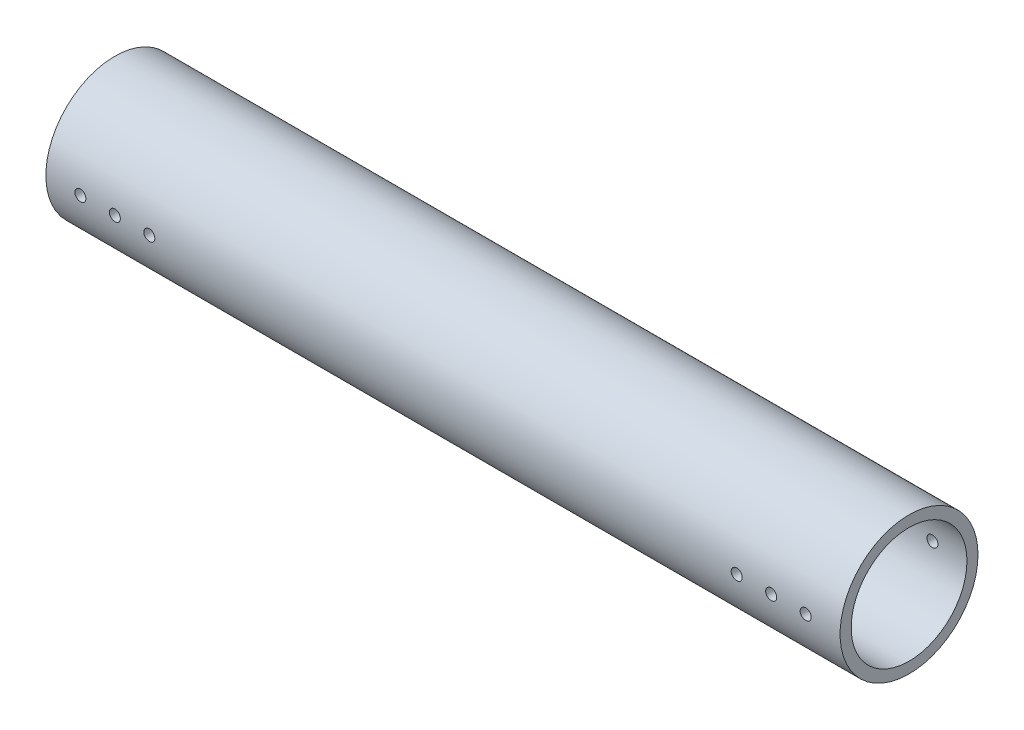
SolidWorks part; units mm, degrees
material "Zoltek Panex 33"
ref_plane "Спереди" through (0, 0, 0) normal (0, 0, 1) x (1, 0, 0)
ref_plane "Сверху" through (0, 0, 0) normal (0, 1, 0) x (1, 0, 0)
ref_plane "Справа" through (0, 0, 0) normal (1, 0, 0) x (0, 0, -1)
other "Configuration Table"
sketch "Эскиз2" plane through (0, 0, 0) normal (1, 0, 0) x (0, 0, -1)
  circle A0 centre (0, 0) radius 25
  circle A1 centre (0, 0) radius 21
  dimension "D1" = 50
  dimension "D2" = 42
extrude "Бобышка-Вытянуть2" add sketch "Эскиз2" along normal blind 288
ref_plane "Плоскость1" through (0, 0, 25) normal (0, 0, 1) x (1, 0, 0)
sketch "Эскиз4" plane through (0, 0, 25) normal (0, 0, 1) x (1, 0, 0)
  line L0 (0, -25) -> (288, -25) construction
  line L1 (288, -25) -> (288, 25) construction
  circle A0 centre (12.5, 0) radius 2
  circle A1 centre (275.5, 0) radius 2
  circle A2 centre (25, 0) radius 2
  circle A3 centre (37.5, 0) radius 2
  circle A4 centre (263, 0) radius 2
  circle A5 centre (250.5, 0) radius 2
  dimension "D1" = 4
  dimension "D4" = 4
  dimension "D6" = 4
  dimension "D8" = 4
  dimension "D10" = 4
  dimension "D11" = 4
  dimension "D2" = 12.5
  dimension "D3" = 25
  dimension "D5" = 12.5
  dimension "D7" = 12.5
  dimension "D9" = 12.5
  dimension "15" = 12.5
  dimension "D12" = 12.5
extrude "Вырез-Вытянуть2" cut sketch "Эскиз4" against normal through all and the other way blind 10 contours A0 | A1 | A2 | A3 | A5 | A4
equation "\"Diameter\"= 50мм"
equation "\"D1@Эскиз2\"= \"Diameter\""
equation "\"Length\"= 288мм"
equation "\"Thickness\"= 4мм"
equation "\"D1@Бобышка-Вытянуть2\"= \"Length\""
equation "\"D2@Эскиз2\" = \"Diameter\" - \"Thickness\" * 2"
equation "\"D4@Эскиз4\"=\"D1@Эскиз4\""
equation "\"D5@Эскиз4\"=\"D2@Эскиз4\""
equation "\"D3@Эскиз4\"=\"Diameter\"/2"
equation "\"D6@Эскиз4\"=\"D1@Эскиз4\""
equation "\"D8@Эскиз4\"=\"D6@Эскиз4\""
equation "\"D10@Эскиз4\"=\"D4@Эскиз4\""
equation "\"D11@Эскиз4\"=\"D4@Эскиз4\""
equation "\"D9@Эскиз4\"=\"D7@Эскиз4\""
